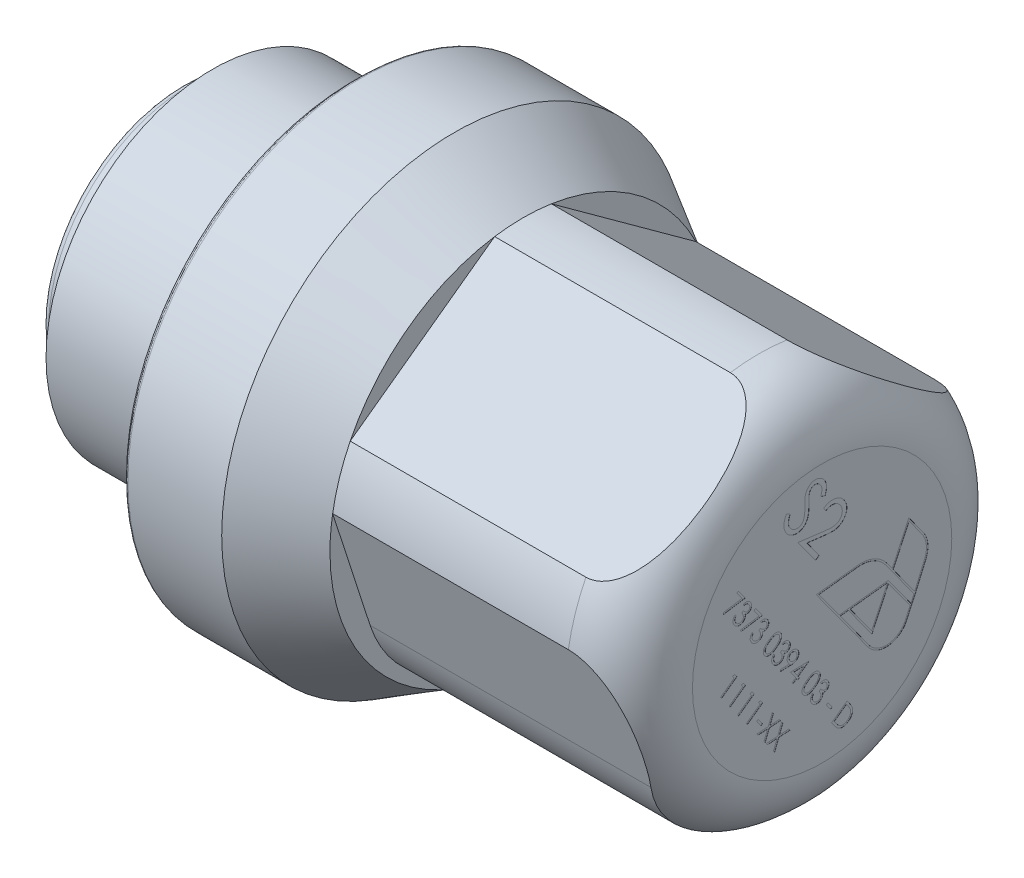
SolidWorks part; units mm, degrees
material "K1045"
ref_plane "Front Plane" through (0, 0, 0) normal (0, 0, 1) x (1, 0, 0)
ref_plane "Top Plane" through (0, 0, 0) normal (0, 1, 0) x (1, 0, 0)
ref_plane "Right Plane" through (0, 0, 0) normal (1, 0, 0) x (0, 0, -1)
sketch "Sketch1" plane through (0, 0, 0) normal (0, 0, 1) x (1, 0, 0)
  line L0 (0, 0) -> (74.478, 0) construction
  line L1 (0, 8.3536) -> (0, 10.5)
  line L2 (11.5, 12) -> (10.36, 13.14)
  line L3 (1.2, 11) -> (2.4355, 13.14)
  line L4 (13.5, 16.7) -> (13.5, 17.7464)
  line L5 (14.1036, 18.35) -> (21.5, 18.35)
  line L6 (13.75, 16.45) -> (15.5, 16.45)
  line L7 (21.5, 18.35) -> (26.9127, 15.225)
  line L8 (7.5, 0) -> (50.5, 0)
  line L9 (26.9127, 15.225) -> (45.5, 15.225)
  line L10 (15.5, 16.45) -> (15.5, 13.25)
  line L11 (13.75, 13.25) -> (15.5, 13.25)
  line L12 (0.6036, 7.75) -> (6, 7.75)
  line L13 (50.5, 10.225) -> (50.5, 0)
  line L14 (13.5, 13) -> (13.5, 12.8)
  line L15 (7.5, 6.25) -> (7.5, 0)
  line L16 (0.0732, 8.1768) -> (0.4268, 7.8232)
  line L17 (10.36, 13.14) -> (2.4355, 13.14)
  line L19 (11.5, 12) -> (12.7, 12)
  line L20 (13.9268, 18.2768) -> (13.5732, 17.9232)
  line L23 (0.5, 11) -> (1.2, 11)
  arc A0 (0.5, 11) -> (0, 10.5) centre (0.5, 10.5) ccw
  arc A1 (13.5, 16.7) -> (13.75, 16.45) centre (13.75, 16.7) ccw
  arc A2 (12.7, 12) -> (13.5, 12.8) centre (12.7, 12.8) ccw
  arc A3 (6, 7.75) -> (7.5, 6.25) centre (6, 6.25) cw
  arc A4 (45.5, 15.225) -> (50.5, 10.225) centre (45.5, 10.225) cw
  arc A5 (13.5, 13) -> (13.75, 13.25) centre (13.75, 13) cw
  arc A6 (0.6036, 7.75) -> (0.4268, 7.8232) centre (0.6036, 8) cw
  arc A7 (0, 8.3536) -> (0.0732, 8.1768) centre (0.25, 8.3536) ccw
  arc A8 (14.1036, 18.35) -> (13.9268, 18.2768) centre (14.1036, 18.1) ccw
  arc A9 (13.5, 17.7464) -> (13.5732, 17.9232) centre (13.75, 17.7464) cw
  point P14 (0, 7.75)
  point P18 (50.5, 12.5)
  point P39 (0.5, 7.75)
  point P42 (0, 8.25)
  point P45 (14, 18.35)
  dimension "D25" = 0.5
  dimension "D27" = 2
  dimension "D7" = 0.5
  dimension "D9" = 5
  dimension "D10" = 45
  dimension "D20" = 1.5
  dimension "D21" = 0.25
  dimension "D6" = 2
  dimension "D16" = 0.8
  dimension "D12" = 0.25
  dimension "D3" = 50.5
  dimension "D4" = 7.5
  dimension "D5" = 3.2
  dimension "D8" = 13.5
  dimension "D11" = 120
  dimension "D13" = 36.7
  dimension "D14" = 8
  dimension "D15" = 26.5
  dimension "D17" = 15.5
  dimension "D18" = 30
  dimension "D19" = 30.45
  dimension "D22" = 22
  dimension "D23" = 26.28
  dimension "D26" = 24
  dimension "D24" = 1.2
  dimension "D28" = 45
revolve "Revolve1" add sketch "Sketch1" angle 360 about L0
cosmetic thread "Cosmetic Thread1" parameters "D2"=24.117
ref_plane "Plane1" through (26.9127, 0, 0) normal (1, 0, 0) x (0, 0, -1)
sketch "Sketch2" plane through (26.9127, 0, 0) normal (1, 0, 0) x (0, 0, -1)
  line L0 (0, 0) -> (23.7491, 0) construction
  line L1 (0, 0) -> (0, 21.3432) construction
  line L2 (0, 16.685) -> (-15.8667, 5.161)
  line L3 (-15.8667, 5.161) -> (-12.0562, -6.5857)
  line L4 (-2.5442, -13.5) -> (2.5442, -13.5)
  line L5 (0, 16.685) -> (15.8667, 5.161)
  line L6 (15.8667, 5.161) -> (12.0562, -6.5857)
  circle A0 centre (0, 0) radius 15.225 construction
  circle A1 centre (0, 0) radius 15.225 construction
  circle A2 centre (0, 0) radius 16.685 construction
  arc A3 (2.5442, -13.5) -> (12.0562, -6.5857) centre (2.5442, -3.5) ccw
  arc A4 (-2.5442, -13.5) -> (-12.0562, -6.5857) centre (-2.5442, -3.5) cw
  point P15 (-9.8132, -13.5)
  point P16 (9.8132, -13.5)
  dimension "D3" = 13.5
  dimension "D2" = 33.37
  dimension "D6" = 13.5
  dimension "D8" = 10
  dimension "D4" = 13.5
  dimension "D5" = 13.5
  dimension "D7" = 13.5
extrude "Extrude1" cut sketch "Sketch2" along normal up to surface (23.5873 mm away) flip side to cut up to face at (50.5, 0, 10.225)
sketch "Sketch3" plane through (50.5, -24.6406, -29.2885) normal (-1, 0, 0) x (0, 0.809, 0.5878)
  line L0 (46.3581, -13.2121) -> (27.7401, -13.2121) construction
  line L1 (37.8157, -7.3573) -> (46.7686, -7.3573) construction
  circle A0 centre (37.15, -9.2115) radius 10.225 construction
  text T0 "7373 0394 03 - D\r\n1111-XX" font "Century Gothic" height 1.5
  text T1 "S2 " font "Century Gothic" height 3.5
  line B0 (31.723, -8.7001) -> (35.6451, -8.7001)
  line B1 (32.3039, -7.9006) -> (35.1905, -7.9006)
  line B2 (35.5769, -8.5801) -> (35.2587, -8.0206)
  line B3 (34.1355, -4.567) -> (34.8196, -4.567)
  line B4 (35.6451, -1.8503) -> (34.1355, -4.567)
  line B5 (32.3039, -7.9006) -> (33.7253, -5.3239)
  line B6 (30.57, -5.3239) -> (30.2115, -5.9435)
  line B7 (33.7203, -1.8503) -> (35.6451, -1.8503)
  line B8 (30.9827, -4.567) -> (30.57, -5.3239)
  line B9 (30.9827, -4.567) -> (32.0193, -2.8191)
  line B10 (35.6451, -8.7001) -> (38.642, -8.7001)
  line B11 (36.9572, -5.7371) -> (38.642, -8.7001)
  line B12 (30.7448, -5.2035) -> (31.0511, -4.687)
  line B13 (33.7203, -1.9703) -> (35.4412, -1.9703)
  line B14 (35.4412, -1.9703) -> (33.9982, -4.567)
  line B15 (34.8196, -4.687) -> (31.0511, -4.687)
  line B16 (36.8544, -5.7991) -> (38.4358, -8.5801)
  line B17 (35.7149, -8.5801) -> (38.4358, -8.5801)
  line B18 (33.7948, -5.2035) -> (30.7448, -5.2035)
  line B19 (35.7149, -8.5801) -> (33.7948, -5.2035)
  line B20 (30.7086, -5.3239) -> (30.314, -6.0059)
  line B21 (31.723, -8.5801) -> (35.5769, -8.5801)
  line B22 (33.9982, -4.567) -> (31.1222, -4.567)
  line B23 (31.1222, -4.567) -> (32.1225, -2.8803)
  line B24 (32.1007, -8.0206) -> (35.2587, -8.0206)
  line B25 (32.1007, -8.0206) -> (33.5882, -5.3239)
  line B26 (33.5882, -5.3239) -> (30.7086, -5.3239)
  line B27 (35.1905, -7.9006) -> (33.7253, -5.3239)
  arc B28 (32.0193, -2.8191) -> (33.7203, -1.8503) centre (33.7203, -3.8279) cw
  arc B29 (31.723, -8.7001) -> (30.2115, -5.9435) centre (31.723, -6.9074) cw
  arc B30 (34.8196, -4.567) -> (36.9572, -5.7371) centre (34.8196, -7.1046) cw
  arc B31 (32.1225, -2.8803) -> (33.7203, -1.9703) centre (33.7203, -3.8279) cw
  arc B32 (34.8196, -4.687) -> (36.8544, -5.7991) centre (34.8196, -7.1046) cw
  arc B33 (31.723, -8.5801) -> (30.314, -6.0059) centre (31.723, -6.9074) cw
sketch_block_instance "SKETCH LOGO-3"
sketch_block "SKETCH LOGO" parameters "D1"=29.059, "D2"=11.4163, "D3"=29.624, "D4"=6.8884
extrude "Cut-Extrude1" cut sketch "Sketch3" along normal blind 0.01
